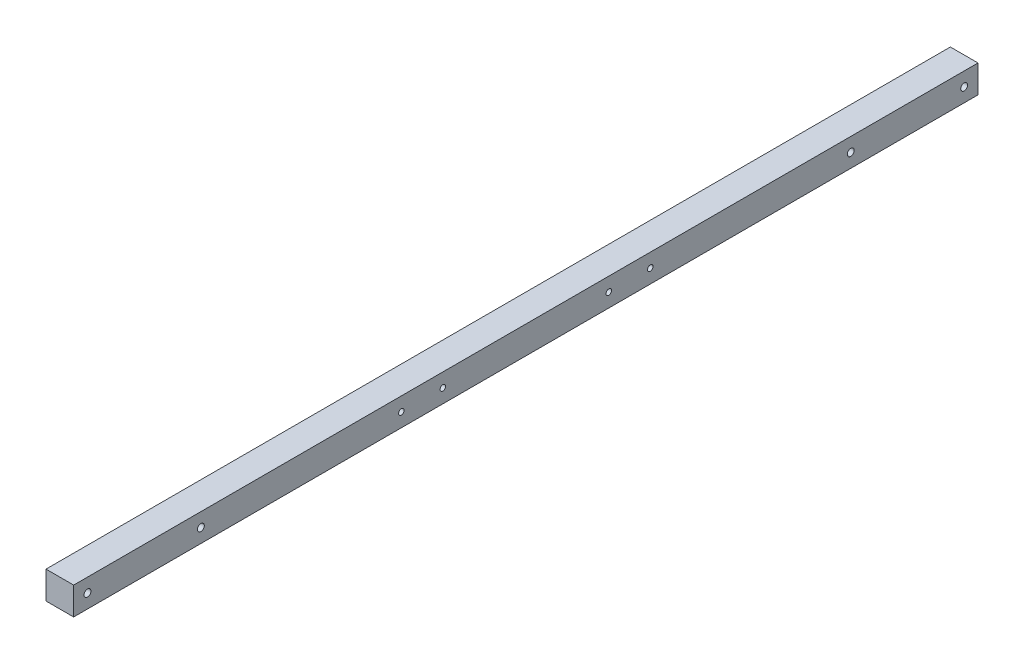
SolidWorks part; units mm, degrees
ref_plane "Front Plane" through (0, 0, 0) normal (0, 0, 1) x (1, 0, 0)
ref_plane "Top Plane" through (0, 0, 0) normal (0, 1, 0) x (1, 0, 0)
ref_plane "Right Plane" through (0, 0, 0) normal (1, 0, 0) x (0, 0, -1)
sketch "Sketch1" plane through (0, 0, 0) normal (0, 0, 1) x (1, 0, 0)
  line L5 (-12.7, -12.7) -> (12.7, -12.7)
  line L6 (-12.7, -12.7) -> (-12.7, 12.7)
  line L7 (-12.7, 12.7) -> (12.7, 12.7)
  line L8 (12.7, -12.7) -> (12.7, 12.7)
  line L9 (-12.7, -12.7) -> (12.7, 12.7) construction
  line L10 (-12.7, 12.7) -> (12.7, -12.7) construction
  point P0 (0, 0)
  dimension "D1" = 25.4
  dimension "D2" = 25.4
extrude "Boss-Extrude1" add sketch "Sketch1" along normal blind 830.58
sketch "Sketch2" plane through (-12.7, 0, 0) normal (1, 0, 0) x (0, 0, -1)
  line L0 (0, 0) -> (-830.58, 0) construction
  line L2 (0, 12.7) -> (0, -12.7) construction
  line L4 (0, -12.7) -> (0, 12.7) construction
  line L5 (-830.58, 12.7) -> (-830.58, -12.7) construction
  circle A0 centre (-12.7, 0) radius 3.175
  circle A2 centre (-116.84, 0) radius 3.175
  dimension "D1" = 6.35
  dimension "D2" = 12.7
  dimension "D3" = 104.14
ref_plane "Plane1" through (0, 0, 415.29) normal (0, 0, -1) x (-1, 0, 0)
extrude "Cut-Extrude4" cut sketch "Sketch2" along normal through all
mirror "Mirror1" about plane through (0, 0, 415.29) normal (0, 0, -1) of "Cut-Extrude4"
hole_wizard "1/4-20 Tapped Hole1" positions "Sketch4" profile "Sketch6" tap size "1/4-20" standard "ANSI Inch"
sketch "Sketch4" plane through (12.7, 0, 0) normal (1, 0, 0) x (0, 0, -1)
  line L2 (-300.99, 0) -> (-529.59, 0) construction
  line L4 (-415.29, 12.7) -> (-415.29, 0) construction
  line L6 (-830.58, 12.7) -> (0, 12.7) construction
  line L7 (-300.99, 0) -> (0, 0) construction
  line L8 (-491.49, 0) -> (-339.09, 0) construction
  point P0 (-300.99, 0)
  point P2 (-529.59, 0)
  point P27 (-491.49, 0)
  point P29 (-339.09, 0)
  point P37 (-415.29, 0)
  dimension "D1" = 228.6
  dimension "D2" = 152.4
sketch "Sketch6" plane through (12.7, 0, 300.99) normal (0, 1, 0) x (0, 0, -1)
  line L0 (0, 0) -> (0, 20.5838)
  line L1 (0, 20.5838) -> (2.5527, 19.05)
  line L2 (2.5527, 19.05) -> (2.5527, 0)
  line L5 (2.5527, 0) -> (0, 0)
  line L10 (0, 20.5838) -> (-2.5527, 19.05) construction
  line L11 (0, -6.35) -> (0, 107.95) construction
  dimension "Tap Drill Dia." = 5.1054
  dimension "Tap Drill Depth" = 19.05
  dimension "Drill Angle" = 118
cosmetic thread "Hole Thread1"
cosmetic thread "Hole Thread2"
cosmetic thread "Hole Thread3"
cosmetic thread "Hole Thread4"
